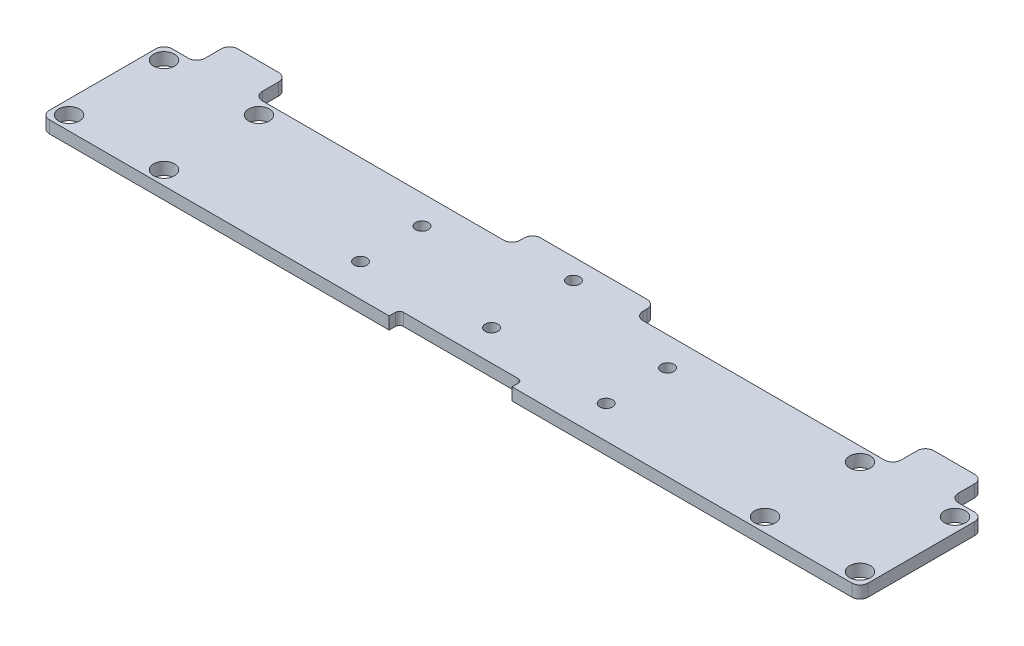
SolidWorks part; units mm, degrees
ref_plane "Alzado" through (0, 0, 0) normal (0, 0, 1) x (1, 0, 0)
ref_plane "Planta" through (0, 0, 0) normal (0, 1, 0) x (1, 0, 0)
ref_plane "Vista lateral" through (0, 0, 0) normal (1, 0, 0) x (0, 0, -1)
sketch "Croquis1" plane through (0, 0, 0) normal (0, 1, 0) x (1, 0, 0)
  line L0 (100, 30) -> (100, 0) construction
  line L1 (0, 0) -> (200, 0)
  line L2 (0, 0) -> (0, 30)
  line L3 (0, 30) -> (8, 30)
  line L4 (200, 0) -> (200, 30)
  line L5 (30, 30) -> (30, 0) construction
  line L6 (30, 30) -> (0, 0) construction
  line L7 (22, 30) -> (85, 30)
  line L8 (3.4, 3.4) -> (26.6, 3.4) construction
  line L9 (3.4, 3.4) -> (3.4, 26.6) construction
  line L10 (3.4, 26.6) -> (26.6, 26.6) construction
  line L11 (26.6, 3.4) -> (26.6, 26.6) construction
  line L12 (3.4, 3.4) -> (26.6, 26.6) construction
  line L13 (3.4, 26.6) -> (26.6, 3.4) construction
  line L15 (8, 30) -> (8, 38)
  line L16 (8, 38) -> (22, 38)
  line L17 (22, 30) -> (22, 38)
  line L18 (178, 30) -> (178, 38)
  line L19 (192, 38) -> (178, 38)
  line L20 (192, 30) -> (192, 38)
  line L21 (192, 30) -> (200, 30)
  line L22 (115, 30) -> (178, 30)
  line L24 (85, 30) -> (85, 35)
  line L25 (85, 35) -> (115, 35)
  line L26 (115, 30) -> (115, 35)
  circle A0 centre (3.4, 26.6) radius 2.55
  circle A1 centre (26.6, 26.6) radius 2.55
  circle A2 centre (26.6, 3.4) radius 2.55
  circle A3 centre (3.4, 3.4) radius 2.55
  circle A4 centre (173.4, 3.4) radius 2.55
  circle A5 centre (196.6, 3.4) radius 2.55
  circle A6 centre (196.6, 26.6) radius 2.55
  circle A7 centre (173.4, 26.6) radius 2.55
  circle A8 centre (100, 30) radius 1.55
  circle A9 centre (100, 10) radius 1.55
  circle A10 centre (70, 23) radius 1.55
  circle A11 centre (70, 8) radius 1.55
  circle A12 centre (130, 8) radius 1.55
  circle A13 centre (130, 23) radius 1.55
  point P9 (15, 15)
  dimension "D6" = 5.1
  dimension "D10" = 3.1
  dimension "D11" = 20
  dimension "D1" = 30
  dimension "D2" = 200
  dimension "D3" = 30
  dimension "D4" = 23.2
  dimension "D5" = 23.2
  dimension "D7" = 14
  dimension "D8" = 8
  dimension "D9" = 8
  dimension "D12" = 5
  dimension "D13" = 30
  dimension "D14" = 15
  dimension "D15" = 5
  dimension "D16" = 30
  dimension "D17" = 15
  dimension "D18" = 7
extrude "Saliente-Extruir1" add sketch "Croquis1" along normal blind 3
fillet "Redondeo2" radius 2 16 edges at (178, 1.5, -38) (192, 1.5, -38) (192, 1.5, -30) (22, 1.5, -30) (22, 1.5, -38) (8, 1.5, -30) (8, 1.5, -38) (0, 1.5, -30) (0, 1.5, 0) (200, 1.5, -30) (200, 1.5, 0) (85, 1.5, -30) (85, 1.5, -35) (115, 1.5, -35) (115, 1.5, -30) (178, 1.5, -30)
sketch "Croquis2" plane through (0, 3, 0) normal (0, 1, 0) x (1, 0, 0)
  line L0 (2, 0) -> (198, 0) construction
  line L1 (85, 0) -> (115, 0)
  line L2 (85, 0) -> (85, 1.5)
  line L3 (86, 2.5) -> (114, 2.5)
  line L4 (115, 0) -> (115, 1.5)
  line L5 (100, 0) -> (100, 23.6106) construction
  arc A1 (114, 2.5) -> (115, 1.5) centre (114, 1.5) cw
  arc A2 (85, 1.5) -> (86, 2.5) centre (86, 1.5) cw
  point P10 (115, 2.5)
  point P13 (85, 2.5)
  dimension "D4" = 1
  dimension "D1" = 30
  dimension "D2" = 2.5
  dimension "D3" = 15
extrude "Cortar-Extruir1" cut sketch "Croquis2" against normal up to surface (3 mm away) up to face at (130, 0, -9.55)
